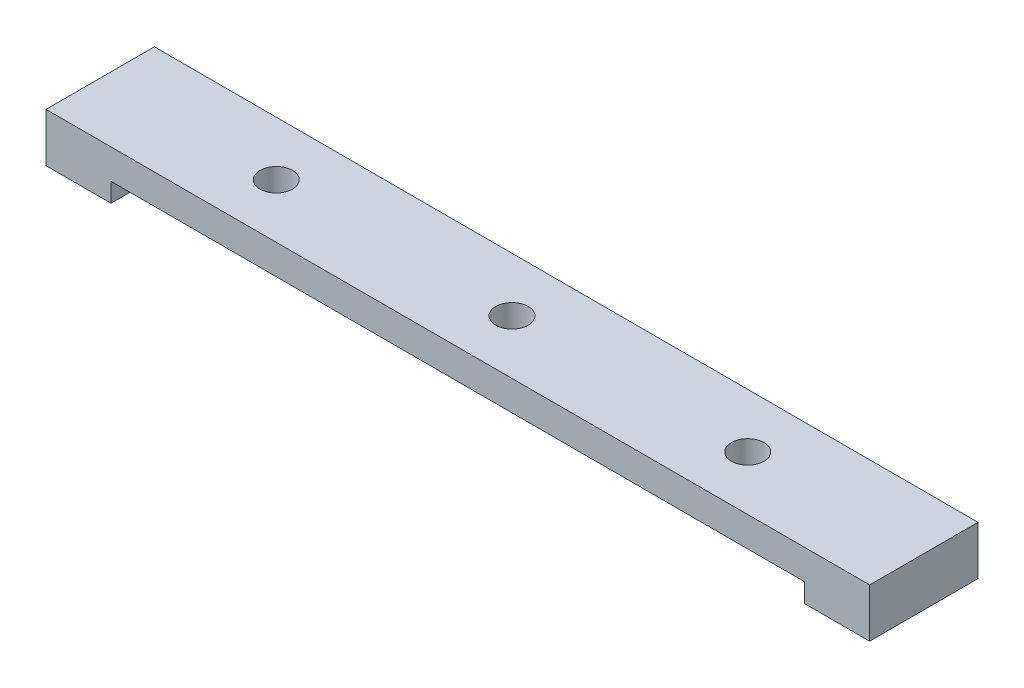
SolidWorks part; units mm, degrees
material "1060 Alloy"
ref_plane "Front Plane" through (0, 0, 0) normal (0, 0, 1) x (1, 0, 0)
ref_plane "Top Plane" through (0, 0, 0) normal (0, 1, 0) x (1, 0, 0)
ref_plane "Right Plane" through (0, 0, 0) normal (1, 0, 0) x (0, 0, -1)
sketch "Sketch1" plane through (0, 0, 0) normal (0, 1, 0) x (1, 0, 0)
  line L1 (0, 0) -> (76, 0)
  line L2 (0, 0) -> (0, 10)
  line L3 (0, 10) -> (76, 10)
  line L4 (76, 0) -> (76, 10)
  circle A0 centre (16.25, 5) radius 1.5
  circle A1 centre (38, 5) radius 1.5
  circle A2 centre (59.75, 5) radius 1.5
  dimension "D3" = 3
  dimension "D4" = 5
  dimension "D5" = 21.75
  dimension "D1" = 10
  dimension "D2" = 76
  dimension "D6" = 21.75
  dimension "D7" = 38
extrude "Boss-Extrude1" add sketch "Sketch1" along normal blind 4.5
sketch "Sketch2" plane through (0, 0, 0) normal (0, -1, 0) x (1, 0, 0)
  line L0 (0, 0) -> (76, 0) construction
  line L1 (6, 0) -> (70, 0)
  line L2 (6, 0) -> (6, -10)
  line L3 (6, -10) -> (70, -10)
  line L4 (70, 0) -> (70, -10)
  line L5 (76, -10) -> (0, -10) construction
  line L6 (0, -10) -> (0, 0) construction
  line L7 (76, 0) -> (76, -10) construction
  dimension "D1" = 6
  dimension "D2" = 6
extrude "Cut-Extrude1" cut sketch "Sketch2" against normal offset from surface (1.75 mm away) 2.75 up to face at (38, 4.5, -3.5)
